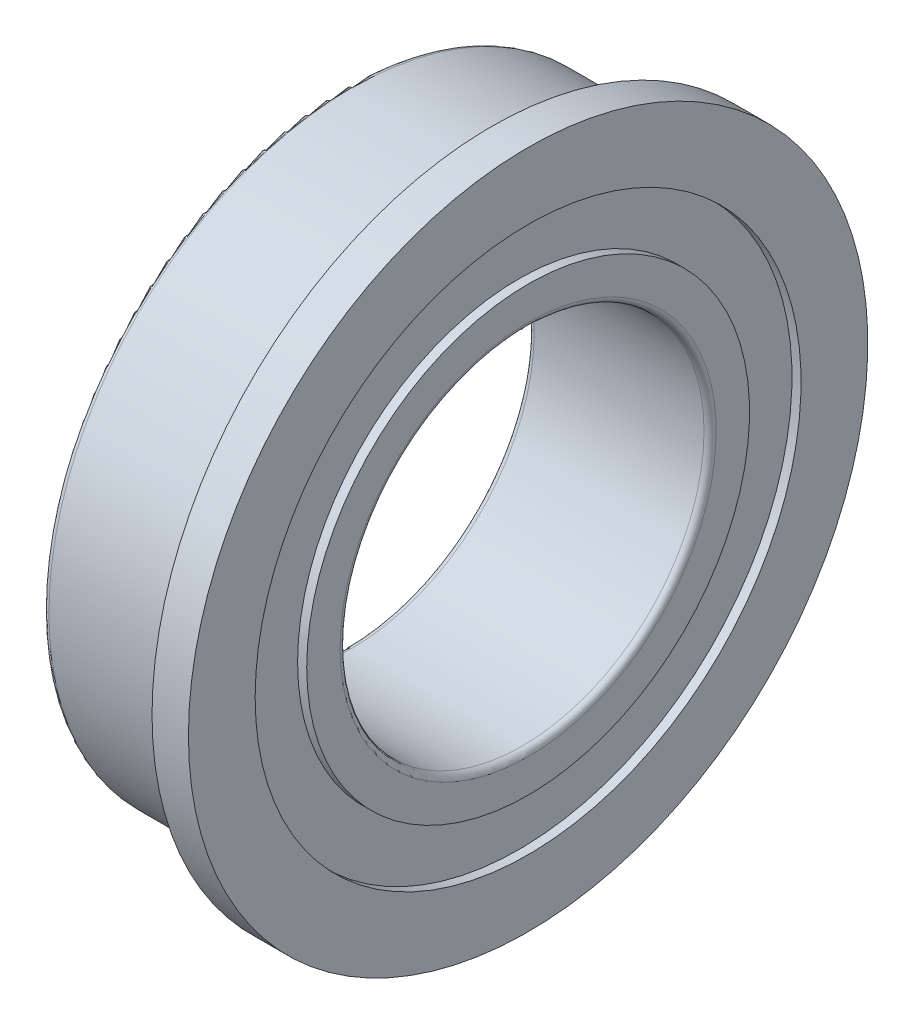
SolidWorks part; units mm, degrees
ref_plane "Front Plane" through (0, 0, 0) normal (0, 0, 1) x (1, 0, 0)
ref_plane "Top Plane" through (0, 0, 0) normal (0, 1, 0) x (1, 0, 0)
ref_plane "Right Plane" through (0, 0, 0) normal (1, 0, 0) x (0, 0, -1)
ref_axis "Axis_X" through (-2.55, 0, 0) along (1, 0, 0)
ref_axis "Axis_Y" through (0, 6.16, 0) along (0, -1, 0)
ref_axis "Axis_Z" through (0, 0, -6.16) along (0, 0, 1)
sketch "Sketch1" plane through (0, 0, 0) normal (0, 0, 1) x (1, 0, 0)
  line L0 (-2.4, 0) -> (0.6, 0) construction
  line L1 (0, 5.2) -> (0, 5.6)
  line L2 (0, 5.6) -> (0.6, 5.6)
  line L3 (0.6, 5.6) -> (0.6, 4.5)
  line L4 (0.5, 3) -> (-2.3, 3)
  line L5 (-2.4, 3.1) -> (-2.4, 3.65)
  line L6 (-2.3, 5) -> (-0.2, 5)
  line L7 (-2.4, 4.5) -> (-2.25, 4.5)
  line L8 (-2.25, 4.5) -> (-2.25, 3.65)
  line L9 (-2.25, 3.65) -> (-2.4, 3.65)
  line L10 (0.6, 4.5) -> (0.45, 4.5)
  line L11 (0.45, 4.5) -> (0.45, 3.65)
  line L12 (0.45, 3.65) -> (0.6, 3.65)
  line L13 (-2.4, 4.5) -> (-2.4, 4.9)
  line L14 (0.6, 3.65) -> (0.6, 3.1)
  arc A0 (-0.2, 5) -> (0, 5.2) centre (0, 5) ccw
  arc A1 (-2.4, 4.9) -> (-2.3, 5) centre (-2.3, 4.9) cw
  arc A2 (-2.3, 3) -> (-2.4, 3.1) centre (-2.3, 3.1) cw
  arc A3 (0.5, 3) -> (0.6, 3.1) centre (0.5, 3.1) ccw
  dimension "R_s" = 0.1
  dimension "FIX_2" = 0.2
  dimension "D" = 10
  dimension "D_s" = 6
  dimension "B" = 3
  dimension "C" = 0.6
  dimension "D1." = 11.2
  dimension "MSM_1" = 7.3
  dimension "MSM_2" = 9
  dimension "FIX_3" = 0.15
revolve "Revolve1" add sketch "Sketch1" angle 360 about axis through (-2.55, 0, 0) along (1, 0, 0)
equation "\"Factor\"= 1.082532"
